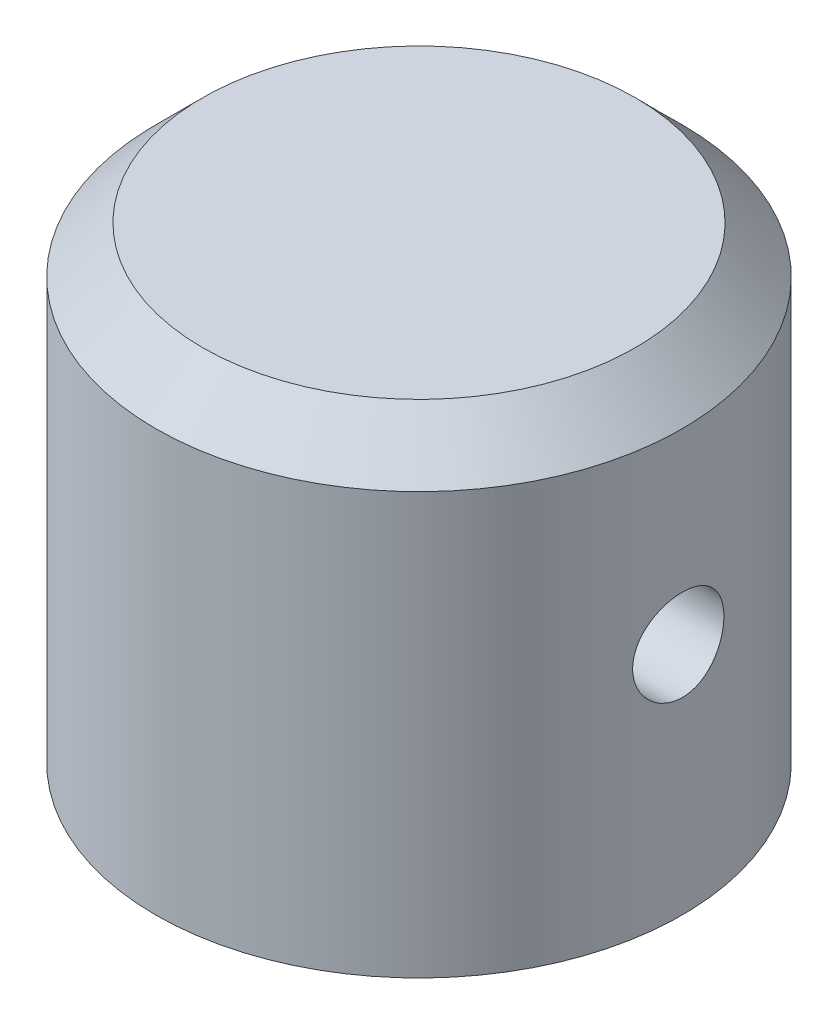
SolidWorks part; units mm, degrees
ref_plane "Front Plane" through (0, 0, 0) normal (0, 0, 1) x (1, 0, 0)
ref_plane "Top Plane" through (0, 0, 0) normal (0, 1, 0) x (1, 0, 0)
ref_plane "Right Plane" through (0, 0, 0) normal (1, 0, 0) x (0, 0, -1)
sketch "Sketch1" plane through (0, 0, 0) normal (0, 1, 0) x (1, 0, 0)
  circle A0 centre (0, 0) radius 14.2875
  dimension "D1" = 28.575
extrude "Boss-Extrude1" add sketch "Sketch1" along normal blind 25.4
sketch "Sketch2" plane through (0, 0, 0) normal (0, -1, 0) x (-1, 0, 0)
  circle A0 centre (0, 0) radius 4
  dimension "D1" = 8
extrude "Cut-Extrude1" cut sketch "Sketch2" against normal blind 8
sketch "Sketch3" plane through (0, 0, 0) normal (1, 0, 0) x (0, 0, -1)
  line L0 (0, 0) -> (0, 12.7) construction
  line L1 (0, 13.97) -> (0, -13.97) construction
  circle A0 centre (0, 12.7) radius 2.4765
  dimension "D2" = 4.953
  dimension "D1" = 12.7
extrude "Cut-Extrude2" cut sketch "Sketch3" against normal through all and the other way through all
chamfer "Chamfer1" distance 2.54 angle 45 1 edges at (0, 25.4, 14.2875)
